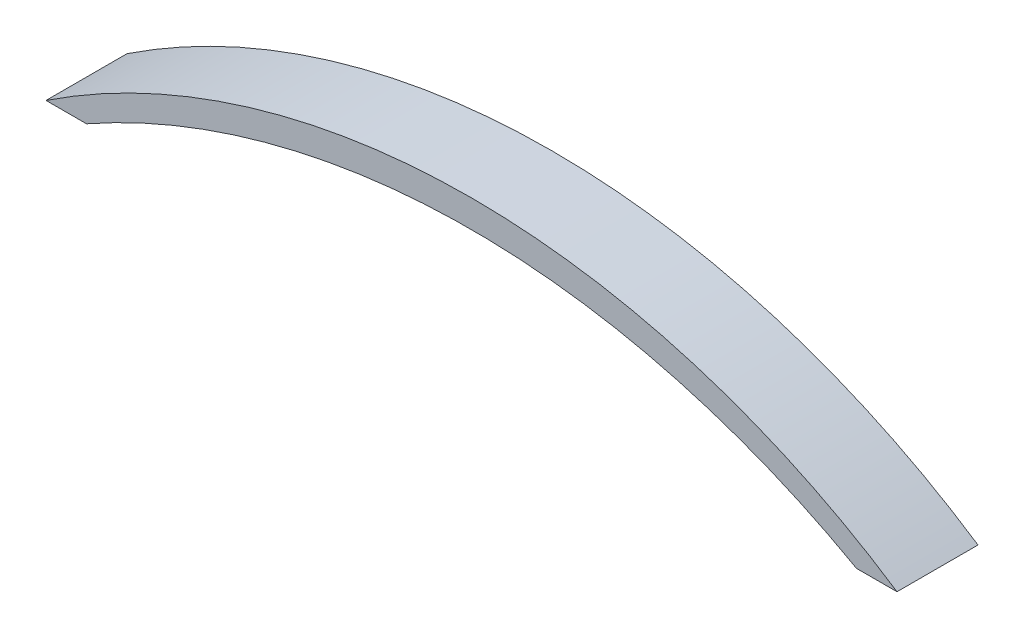
SolidWorks part; units mm, degrees
ref_plane "Front Plane" through (0, 0, 0) normal (0, 0, 1) x (1, 0, 0)
ref_plane "Top Plane" through (0, 0, 0) normal (0, 1, 0) x (1, 0, 0)
ref_plane "Right Plane" through (0, 0, 0) normal (1, 0, 0) x (0, 0, -1)
sketch "Sketch1" plane through (0, 0, 0) normal (0, 0, 1) x (1, 0, 0)
  line L0 (0, 0) -> (5, 0)
  line L1 (105.0571, 0) -> (100.0571, 0)
  arc A0 (0, 0) -> (105.0571, 0) centre (52.5286, -79.1312) cw
  arc A1 (5, 0) -> (100.0571, 0) centre (52.5286, -84.4689) cw
extrude "Boss-Extrude1" add sketch "Sketch1" along normal blind 10
scale "Scale1" scale about centroid uniform scaling yes scale factor 0.5
